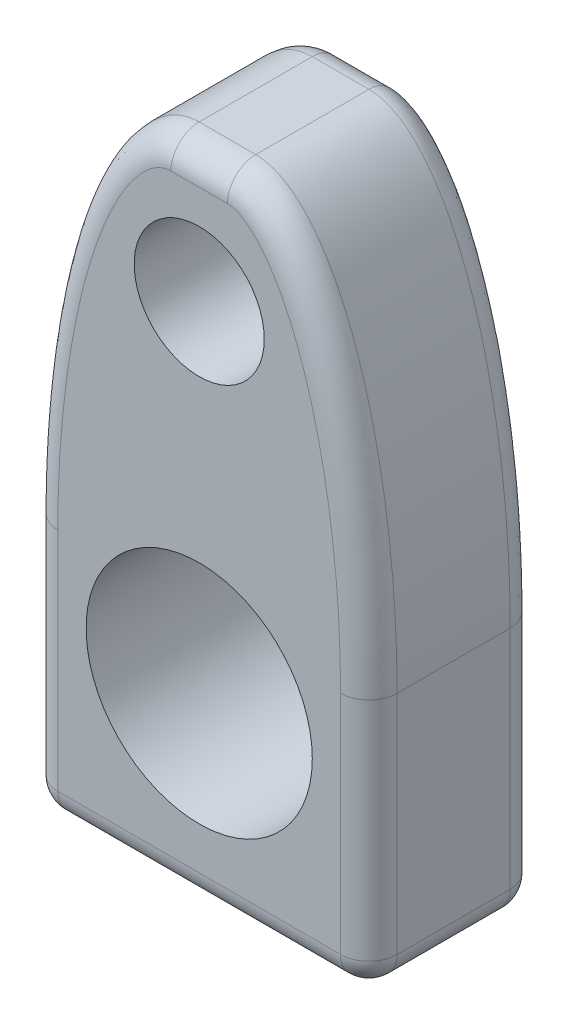
SolidWorks part; units mm, degrees
ref_plane "Front Plane" through (0, 0, 0) normal (0, 0, 1) x (1, 0, 0)
ref_plane "Top Plane" through (0, 0, 0) normal (0, 1, 0) x (1, 0, 0)
ref_plane "Right Plane" through (0, 0, 0) normal (1, 0, 0) x (0, 0, -1)
sketch "Sketch1" plane through (0, 0, 0) normal (0, 0, 1) x (1, 0, 0)
  line L1 (0, 0) -> (12, 0)
  line L2 (0, 0) -> (0, 23)
  line L3 (0, 23) -> (12, 23)
  line L4 (12, 0) -> (12, 23)
  dimension "D1" = 12
  dimension "D2" = 23
extrude "Boss-Extrude1" add sketch "Sketch1" along normal blind 6
sketch "Sketch2" plane through (0, 0, 6) normal (0, 0, 1) x (1, 0, 0)
  line L0 (0, 23) -> (0, 0) construction
  line L1 (12, 23) -> (0, 23) construction
  circle A0 centre (6, 18.5) radius 2.3
  circle A1 centre (6, 6.5) radius 4
  dimension "D1" = 12
  dimension "D2" = 6
  dimension "D3" = 4.6
  dimension "D4" = 4.5
  dimension "D5" = 8
  dimension "D6" = 6
extrude "Cut-Extrude1" cut sketch "Sketch2" against normal blind 6
ref_plane "Plane1" through (6, 0, 0) normal (1, 0, 0) x (0, 0, -1)
fillet "taper_fillet" radius 5 1 edges at (0, 23, 3) second distance 14 tangent propagation no first distance on face at (6, 23, 3)
fillet "taper_fillet2" radius 14 1 edges at (12, 23, 3) second distance 5 first distance on face at (12, 11.5, 3)
fillet "edge_fillets" radius 1 14 edges at (0, 0, 3) (6, 0, 6) (12, 0, 3) (6, 0, 0)
